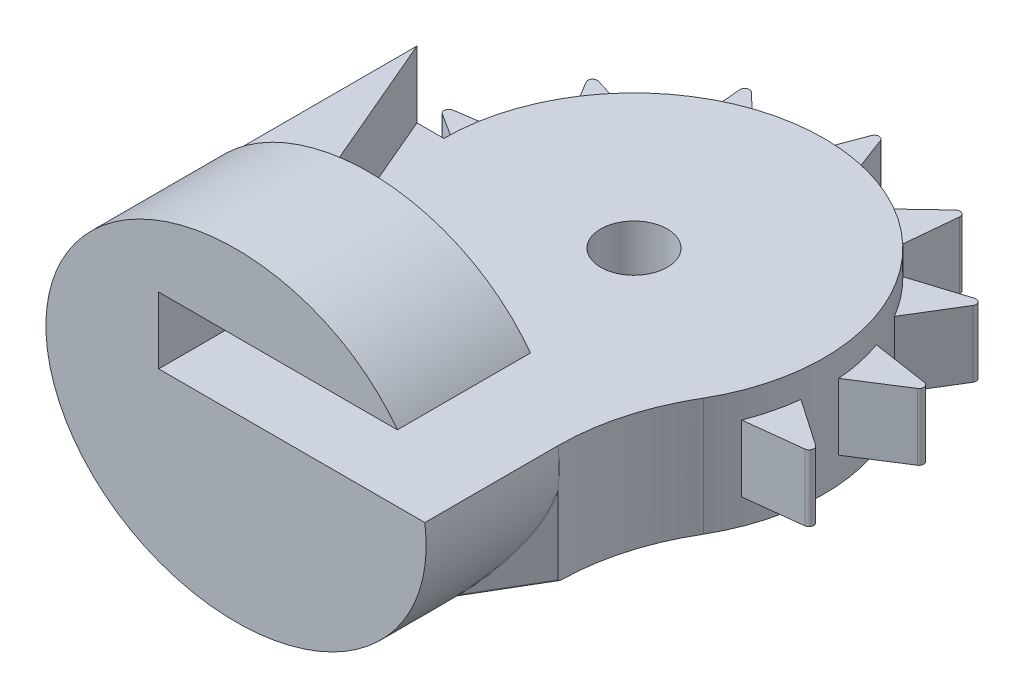
SolidWorks part; units mm, degrees
ref_plane "Front Plane" through (0, 0, 0) normal (0, 0, 1) x (1, 0, 0)
ref_plane "Top Plane" through (0, 0, 0) normal (0, 1, 0) x (1, 0, 0)
ref_plane "Right Plane" through (0, 0, 0) normal (1, 0, 0) x (0, 0, -1)
sketch "Sketch1" plane through (0, 0, 0) normal (0, 0, 1) x (1, 0, 0)
  line L3 (0, 8.5) -> (0, 1) construction
  line L4 (0, 8.5) -> (0, 4.5) construction
  line L5 (8.4837, 4.5) -> (-4.0694, 4.5)
  line L6 (9.9306, 1) -> (-4.0694, 1)
  line L7 (-4.0694, 1) -> (-4.0694, 4.5)
  ellipse E0 centre (0, 0) end of major axis (10, 0) minor radius 8.5 (8.4837, 4.5) -> (9.9306, 1) ccw
  dimension "D1" = 20
  dimension "D2" = 17
  dimension "D5" = 7.5
  dimension "D6" = 4
  dimension "D7" = 14
extrude "Boss-Extrude1" add sketch "Sketch1" along normal blind 7
sketch "Sketch3" plane through (0, 1, 0) normal (0, 1, 0) x (1, 0, 0)
  line L0 (-10, 0) -> (-10, 11)
  line L2 (-10, 0) -> (9.9306, 0)
  line L3 (9.9306, 0) -> (9.9306, 6) construction
  line L4 (13.6383, 6) -> (2.9306, 6) construction
  line L5 (-10, 11) -> (-7.0694, 11)
  arc A0 (11.5309, 5.8976) -> (-7.0694, 11) centre (2.9306, 11) ccw
  circle A1 centre (2.9306, 11) radius 1.75
  spline S0 degree 3 poles (9.9306, 0) (9.9306, 2.345) (10.6138, 4.3483) (11.5908, 6) knots 0 0 0 0 1 1 1 1
  point P1 (0, 0)
  line M1 (9.9306, 0) -> (-4.0694, 0)
  dimension "D3" = 20
  dimension "D5" = 3.5
  dimension "D1" = 11
  dimension "D4" = 6
extrude "Boss-Extrude2" add sketch "Sketch3" against normal blind 6.2 contours S0 A0 L5 L0 L2 A1 M1 region at (1.5738, 1, -9.4603)
sketch "Sketch5" plane through (0, 0, 0) normal (0, 0, -1) x (-1, 0, 0)
  line L0 (4.0694, 1) -> (4.0694, 4.5) construction
  line L1 (4.0694, 1) -> (9.9306, 1) construction
  line L2 (4.0694, 4.5) -> (9.9306, 4.5)
  line L3 (4.0694, 4.5) -> (4.0694, 1)
  line L4 (4.0694, 1) -> (9.9306, 1)
  line L5 (9.9306, 4.5) -> (9.9306, 1)
extrude "Boss-Extrude3" add sketch "Sketch5" along normal blind 11
sketch "Sketch4" plane through (0, 0, 0) normal (0, 0, -1) x (-1, 0, 0)
  line L0 (10, -5.2) -> (10, 1) construction
  line L1 (7.9266, 5.1821) -> (11.8077, 5.1821)
  line L2 (11.8077, 5.1821) -> (11.8077, -5.8086)
  line L3 (11.8077, -5.8086) -> (7.3008, -5.8086)
  ellipse E0 centre (0, 0) end of major axis (10, 0) minor radius 8.5 (7.3008, -5.8086) -> (7.9266, 5.1821) ccw
extrude "Cut-Extrude1" cut sketch "Sketch4" along normal blind 11
sketch "Sketch8" plane through (0, 4.5, 0) normal (0, 1, 0) x (1, 0, 0)
  line L0 (-8.4837, 11) -> (-4.0694, 11)
  line L1 (-4.0694, 11) -> (-4.0694, 0.6532)
  line L2 (-4.0694, 0.6532) -> (-8.4837, 11)
  line L3 (-4.0694, 11) -> (-4.0694, 0) construction
extrude "Cut-Extrude6" cut sketch "Sketch8" against normal blind 3.5
sketch "Sketch10" plane through (0, -5.2, 0) normal (0, -1, 0) x (1, 0, 0)
  line L0 (9.9306, 0) -> (6.7178, 0)
  line L1 (-7.9104, 0) -> (7.9104, 0) construction
  line L2 (6.7178, 0) -> (6.7178, 5.4696)
  line L3 (6.7178, 5.4696) -> (9.9306, 0)
extrude "Boss-Extrude7" add sketch "Sketch10" against normal blind 4
fillet "Fillet2" radius 0.1 3 edges at (7.9104, -5.2, 1.7196) (8.6809, -4.2194, 2.1274) (8.9205, -5.2, 1.7196)
ref_plane "Plane1" through (0, -2.1, 0) normal (0, 1, 0) x (1, 0, 0)
sketch "Sketch11" plane through (0, -2.1, 0) normal (0, 1, 0) x (1, 0, 0)
  line L0 (2.9306, 20.3509) -> (4.4306, 20.3509) construction
  line L1 (4.4306, 20.3509) -> (2.9306, 24.3509)
  line L2 (2.9306, 24.3509) -> (1.4306, 20.3509)
  line L3 (1.4306, 20.3509) -> (4.4306, 20.3509)
  dimension "D1" = 4
  dimension "D2" = 3
  dimension "D3" = 1.5
extrude "Boss-Extrude8" add sketch "Sketch11" along normal blind 1.75 and the other way blind 1.75
pattern_circular "CirPattern1" count 5 every 26 about axis through (2.9306, 1, -11) along (0, 1, 0) of "Boss-Extrude8" reverse direction yes
pattern_circular "CirPattern2" count 4 every 26 about axis through (2.9306, 1, -11) along (0, 1, 0) of "Boss-Extrude8"
fillet "Fillet5" radius 0.25 8 edges at (2.9306, -2.1, -24.3509) (15.8849, -2.1, -7.7701) (15.9897, -2.1, -13.7758) (13.4512, -2.1, -19.2197) (8.7832, -2.1, -22.9997) (-10.1286, -2.1, -13.7758) (-7.5901, -2.1, -19.2197) (-2.9221, -2.1, -22.9997)
